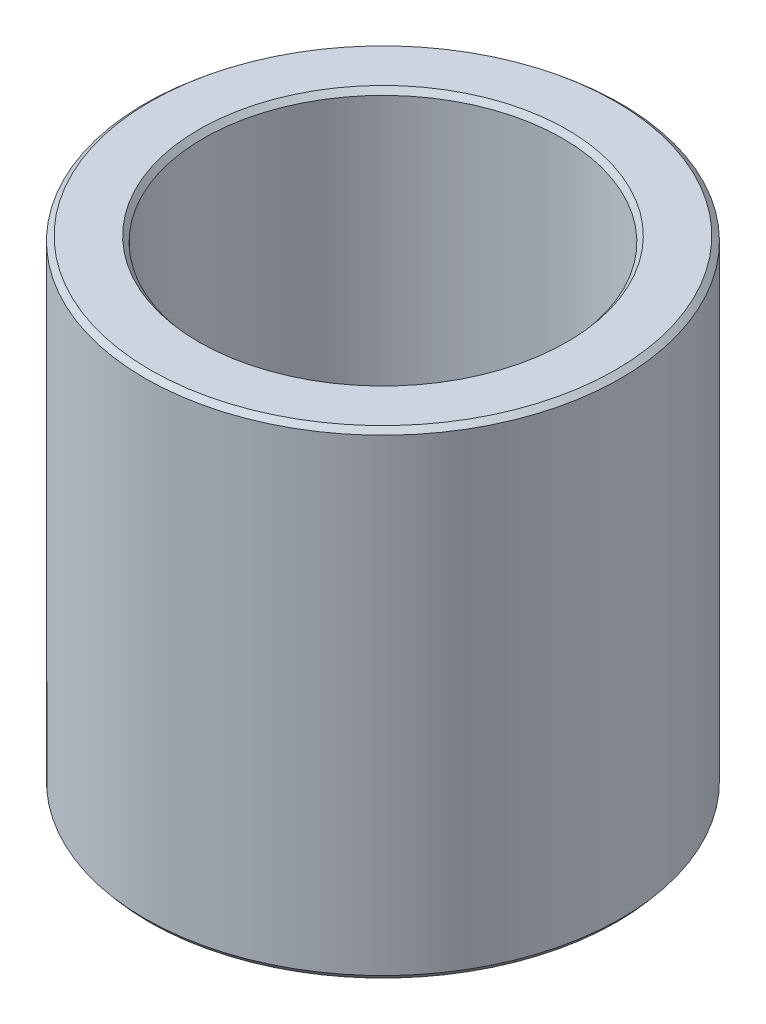
SolidWorks part; units mm, degrees
ref_plane "Front Plane" through (0, 0, 0) normal (0, 0, 1) x (1, 0, 0)
ref_plane "Top Plane" through (0, 0, 0) normal (0, 1, 0) x (1, 0, 0)
ref_plane "Right Plane" through (0, 0, 0) normal (1, 0, 0) x (0, 0, -1)
sketch "Sketch1" plane through (0, 0, 0) normal (0, 1, 0) x (1, 0, 0)
  circle A0 centre (0, 0) radius 27.5
  dimension "SLEEVE_OD" = 55
extrude "Boss-Extrude1" add sketch "Sketch1" along normal blind 55.2294
sketch "Sketch2" plane through (0, 0, 0) normal (0, 1, 0) x (1, 0, 0)
  circle A0 centre (0, 0) radius 20.7542
  dimension "BORE_D" = 41.5084
extrude "Cut-Extrude1" cut sketch "Sketch2" along normal through all
chamfer "Chamfer1" distance 0.5232 angle 50.017 4 edges at (0, 55.2294, 20.7542) (0, 0, 20.7542) (0, 0, 27.5) (0, 55.2294, 27.5) first distance on face at (0, 55.2294, 20.7542) first distance on face at (0, 0, 20.7542) first distance on face at (0, 55.2294, 27.5)
